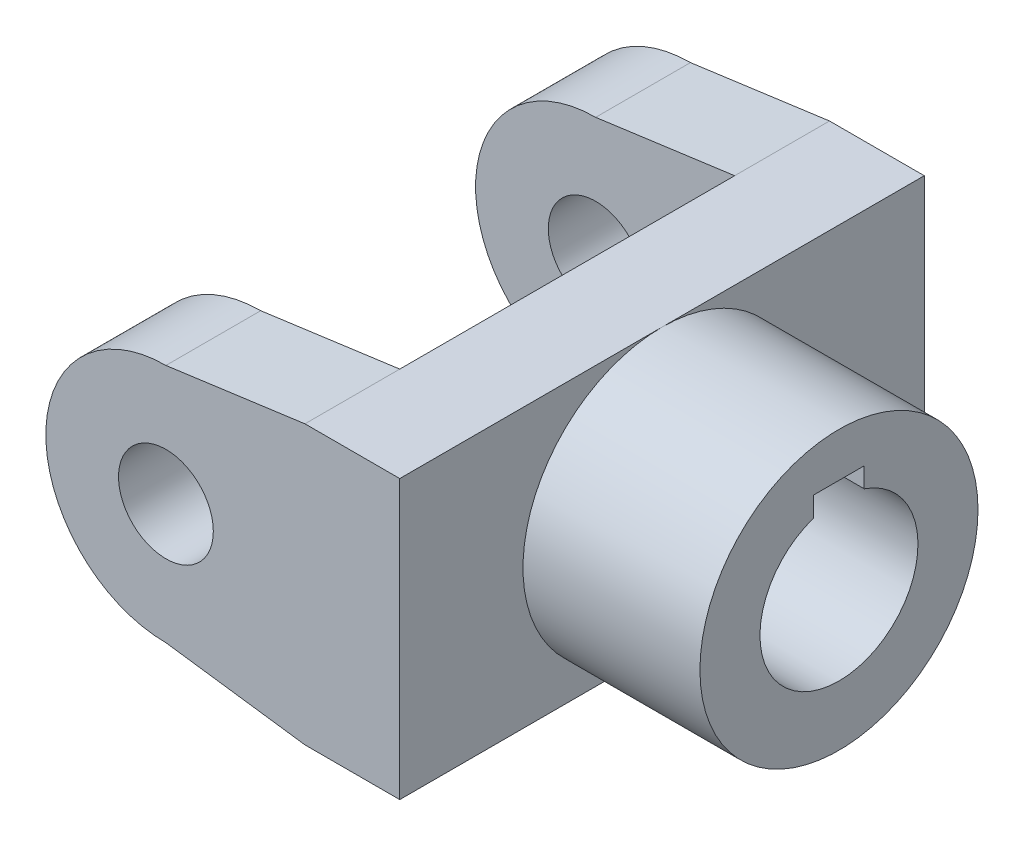
SolidWorks part; units mm, degrees
ref_plane "Front Plane" through (0, 0, 0) normal (0, 0, 1) x (1, 0, 0)
ref_plane "Top Plane" through (0, 0, 0) normal (0, 1, 0) x (1, 0, 0)
ref_plane "Right Plane" through (0, 0, 0) normal (1, 0, 0) x (0, 0, -1)
sketch "Sketch1" plane through (0, 0, 0) normal (0, 0, 1) x (1, 0, 0)
  line L0 (-28, 44) -> (-58, 44)
  line L1 (-28, -44) -> (28, -44)
  line L2 (-28, -44) -> (-28, 44)
  line L3 (-28, 44) -> (28, 44)
  line L4 (28, -44) -> (28, 44)
  line L5 (-28, -44) -> (28, 44) construction
  line L6 (-28, 44) -> (28, -44) construction
  line L8 (-58, 44) -> (-102, 38)
  line L9 (-102, -38) -> (-58, -44)
  line L10 (-58, -44) -> (-28, -44)
  arc A0 (-102, 38) -> (-102, -38) centre (-102, 0) ccw
  circle A1 centre (-102, 0) radius 15
  point P0 (0, 0)
  dimension "D1" = 56
  dimension "D2" = 88
  dimension "D3" = 30
extrude "Boss-Extrude1" add sketch "Sketch1" along normal mid plane 88 contours L1 L4 L3 L2 region at (0, 0, 0)
extrude "Boss-Extrude2" add sketch "Sketch1<3>" along normal mid plane 166 contours L8 A0 L9 L10 L2 L0 A1 region at (-76.3269, 0, 0)
sketch "Sketch1<3>" plane through (0, 0, 0) normal (0, 0, 1) x (1, 0, 0) same geometry as "Sketch1"
sketch "Sketch2" plane through (0, 0, 0) normal (0, 1, 0) x (1, 0, 0)
  line L1 (-140, 83) -> (-140, -83) construction
  line L2 (-140, -53) -> (-58, -53)
  line L3 (-183.126, 0) -> (57.2108, 0) construction
  line L5 (-140, 53) -> (-58, 53)
  line L6 (-58, -53) -> (-58, 53)
  line L7 (-140, -53) -> (-140, 53)
extrude "Cut-Extrude1" cut sketch "Sketch2" against normal mid plane 166 contours L7 L2 L6 L5
sketch "Sketch3" plane through (28, 0, 0) normal (1, 0, 0) x (0, 0, -1)
  line L0 (-44, 0) -> (-44, 44)
  line L1 (-44, 44) -> (0, 44)
  line L2 (0, 44) -> (44, 44)
  line L3 (44, 44) -> (44, 0)
  line L4 (44, 0) -> (44, -44)
  line L5 (44, -44) -> (0, -44)
  line L6 (0, -44) -> (-44, -44)
  circle A0 centre (0, 0) radius 25
  circle A1 centre (0, 0) radius 44
  line M3 (44, -44) -> (44, 44)
  line M4 (44, 44) -> (-44, 44)
  line M5 (-44, 44) -> (-44, -44)
  line M6 (-44, -44) -> (44, -44)
extrude "Cut-Extrude2" cut sketch "Sketch3" against normal blind 56 contours A1 M4 M5 | A1 M3 M4 | A1 M6 M3 | A1 M5 M6 region at (28, 34.1718, 34.1718) region at (28, -34.1718, 34.1718) region at (28, 34.1718, -34.1718) region at (28, -34.1718, -34.1718)
extrude "Cut-Extrude3" cut sketch "Sketch3<4>" against normal blind 196 contours A0 region at (28, 0, 0)
sketch "Sketch3<4>" plane through (28, 0, 0) normal (1, 0, 0) x (0, 0, -1) same geometry as "Sketch3"
sketch "Sketch5" plane through (28, 0, 0) normal (1, 0, 0) x (0, 0, -1)
  line L4 (-8, 30) -> (8, 30)
  line L5 (-8, 30) -> (-8, 23.6854)
  line L6 (8, 30) -> (8, 23.6854)
  arc A0 (8, 23.6854) -> (-8, 23.6854) centre (0, 0) ccw
  arc A2 (4, 24.6779) -> (-4, 24.6779) centre (0, 0) ccw
  point P9 (0, 30)
  point P12 (0, 30)
  circle M7 centre (0, 0) radius 25
extrude "Cut-Extrude6" cut sketch "Sketch5" against normal blind 246 contours L6 L4 L5 A0 M7 region at (28, 27.2692, 0)
